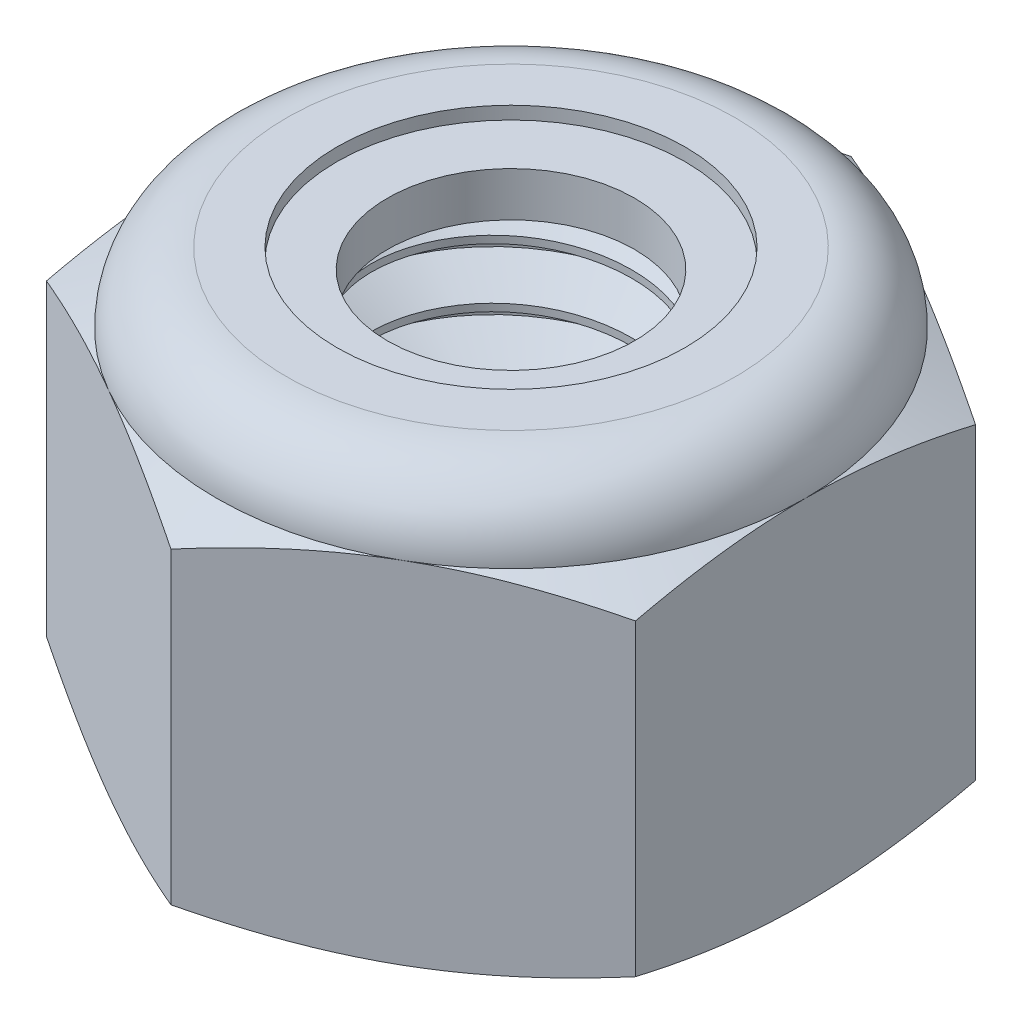
SolidWorks part; units mm, degrees
ref_plane "Front" through (0, 0, 0) normal (0, 0, 1) x (1, 0, 0)
ref_plane "Top" through (0, 0, 0) normal (0, 1, 0) x (1, 0, 0)
ref_plane "Right" through (0, 0, 0) normal (1, 0, 0) x (0, 0, -1)
sketch "Sketch1" plane through (0, 0, 0) normal (0, 1, 0) x (1, 0, 0)
  line L1 (0, 4.0415) -> (-3.5, 2.0207)
  line L2 (-3.5, 2.0207) -> (-3.5, -2.0207)
  line L3 (-3.5, -2.0207) -> (0, -4.0415)
  line L4 (0, -4.0415) -> (3.5, -2.0207)
  line L5 (3.5, -2.0207) -> (3.5, 2.0207)
  line L6 (3.5, 2.0207) -> (0, 4.0415)
  circle A0 centre (0, 0) radius 3.5 construction
  dimension "Hex Flats" = 7
extrude "Extrude1" add sketch "Sketch1" along normal blind 5
sketch "Sketch2" plane through (0, 0, 0) normal (1, 0, 0) x (0, 0, -1)
  line L0 (-2, 0) -> (-2, 5) construction
  line L1 (0, 0) -> (2, 0)
  line L2 (0, 0) -> (0, 5)
  line L3 (0, 5) -> (2, 5)
  line L4 (2, 0) -> (2, 5)
  line L5 (-2.0207, 5) -> (2.0207, 5) construction
  line L7 (0, -2) -> (0, 0) construction
  dimension "Thread Dia" = 4
revolve "Revolve1" add sketch "Sketch2" angle 360 about L7
sketch "Sketch8" plane through (0, 0, 0) normal (0, -1, 0) x (1, 0, 0)
  circle A1 centre (0, 0) radius 2
  circle A2 centre (0, 0) radius 2
  dimension "D1" = 0
curve "Helix/Spiral1" pitch 0.7 height 5.7 turns 8.1429 parameters "Pitch"=0.7
sketch "Sketch10" plane through (0, 0, 0) normal (0, -1, 0) x (1, 0, 0)
  circle A1 centre (0, 0) radius 2
  circle A2 centre (0, 0) radius 2
  dimension "D1" = 0
extrude "Boss-Extrude1" add sketch "Sketch10" against normal through all draft 45
sketch "Sketch11" plane through (0, 5, 0) normal (0, 1, 0) x (1, 0, 0)
  circle A1 centre (0, 0) radius 2
  circle A2 centre (0, 0) radius 2
  dimension "D1" = 0
extrude "Boss-Extrude2" add sketch "Sketch11" against normal through all draft 45
sketch "Sketch9" plane through (0, 0, 0) normal (1, 0, 0) x (0, 0, -1)
  line L0 (2, -0.6125) -> (2, 0)
  line L1 (2, -0.6125) -> (1.5453, -0.35)
  line L2 (1.5453, -0.35) -> (1.5453, -0.2625)
  line L3 (1.5453, -0.2625) -> (2, 0)
  line L4 (-2, 0) -> (2, 0) construction
  line L5 (2, -0.3063) -> (1.5453, -0.3063) construction
  line L6 (1.7727, -0.4813) -> (1.7727, -0.1313) construction
  dimension "D1" = 0.0875
  dimension "D2" = 0.35
  dimension "D3" = 60
sweep "Cut-Sweep1" cut profiles "Sketch9" path "Helix/Spiral1"
combine bodies "Combine1" operation type subtract main body 108 bodies to subtract 132
sketch "Sketch5" plane through (0, 0, 0) normal (1, 0, 0) x (0, 0, -1)
  line L0 (0, 0) -> (3.5, 0)
  line L1 (3.5, 0) -> (4.0415, 0.2525)
  line L2 (4.0415, 0.2525) -> (4.0415, 3.9142)
  line L3 (4.0415, 3.9142) -> (3.5, 4.1667)
  line L4 (2.6667, 5) -> (2.6667, 6.27)
  line L5 (2.6667, 6.27) -> (5.3115, 6.27)
  line L6 (5.3115, 6.27) -> (5.3115, -1.27)
  line L7 (5.3115, -1.27) -> (0, -1.27)
  line L8 (0, -1.27) -> (0, 0)
  line L9 (3.5, 4.1667) -> (3.5, 0) construction
  line L10 (0, 0) -> (2, 0) construction
  line L13 (4.0415, 2.0833) -> (5.3115, 2.0833) construction
  line L14 (4.0415, 5) -> (4.0415, 0) construction
  line L15 (0, 0) -> (0, 6.27) construction
  line L20 (0, 6.27) -> (2.6667, 6.27) construction
  line L22 (0, 5) -> (2, 5) construction
  arc A0 (3.5, 4.1667) -> (2.6667, 5) centre (2.6667, 4.1667) ccw
  dimension "D1" = 25
  dimension "D2" = 1.27
  dimension "D3" = 5
  dimension "D4" = 0.8333
revolve "Cut-Revolve3" cut sketch "Sketch5" angle 360 about L15
sketch "Sketch6" plane through (0, 0, 0) normal (1, 0, 0) x (0, 0, -1)
  line L0 (0, 4.1667) -> (3.3476, 4.1667)
  line L1 (2.6667, 4.8476) -> (2.0681, 4.8476)
  line L2 (0, 6.27) -> (0, 4.1667)
  line L3 (2.0681, 6.27) -> (0, 6.27)
  line L4 (0, 6.27) -> (2.6667, 6.27) construction
  line L5 (0, 0) -> (0, 6.27) construction
  line L6 (0, 6.27) -> (0, 0) construction
  line L7 (2.0681, 4.8476) -> (2.0681, 6.27)
  line L8 (2.6667, 5) -> (2.6667, 4.8476) construction
  line L9 (2.0681, 4.8476) -> (1.4696, 4.8476) construction
  line L10 (1.4696, 4.8476) -> (1.4696, 0) construction
  line L13 (1.4696, 4.6062) -> (2, 4.3) construction
  line L15 (2, 0) -> (2, 5) construction
  line L16 (1.4696, 4.6937) -> (2, 5) construction
  line L19 (1.7348, 4.4531) -> (1.7348, 4.8469) construction
  line L20 (1.4696, 4.6062) -> (1.4696, 4.6937) construction
  line L21 (2, 4.3) -> (2, 5) construction
  line L22 (2, 4.65) -> (1.4696, 4.65) construction
  arc A0 (3.3476, 4.1667) -> (2.6667, 4.8476) centre (2.6667, 4.1667) ccw
  arc A1 (3.5, 4.1667) -> (2.6667, 5) centre (2.6667, 4.1667) ccw construction
  dimension "D1" = 0.1524
  dimension "D2" = 0.7
  dimension "D3" = 0.0875
  dimension "D4" = 60
revolve "Cut-Revolve4" cut sketch "Sketch6" angle 360 about L6
sketch "Sketch7" plane through (0, 0, 0) normal (1, 0, 0) x (0, 0, -1)
  line L0 (1.4696, 4.2429) -> (3.2666, 4.2429)
  line L1 (2.6667, 4.7714) -> (1.4696, 4.7714)
  line L2 (1.4696, 4.7714) -> (1.4696, 4.2429)
  line L3 (1.4696, 4.2429) -> (0, 4.2429) construction
  line L4 (0, 4.2429) -> (0, 4.7714) construction
  line L5 (0, 4.7714) -> (1.4696, 4.7714) construction
  line L6 (1.4696, 4.2429) -> (1.4696, 4.1667) construction
  line L7 (0, 4.1667) -> (3.3476, 4.1667) construction
  line L8 (2.6667, 4.7714) -> (2.6667, 4.8476) construction
  line L9 (1.4696, 4.8476) -> (1.4696, 0) construction
  arc A0 (3.2666, 4.2429) -> (2.6667, 4.7714) centre (2.6667, 4.1667) ccw
  arc A2 (3.3476, 4.1667) -> (2.6667, 4.8476) centre (2.6667, 4.1667) ccw construction
  dimension "D1" = 0.0762
revolve "Revolve2" add sketch "Sketch7" angle 360 about L4
equation "\"D4@Sketch5\"=\"Height@Extrude1\"/6"
equation "\"D3@Helix/Spiral1\"=\"Pitch@Helix/Spiral1\"+\"Height@Extrude1\""
equation "\"D1@Sketch9\"=\"Pitch@Helix/Spiral1\"*.125"
equation "\"D2@Sketch9\"=\"Pitch@Helix/Spiral1\"*.50"
equation "\"D2@Sketch6\"=\"Pitch@Helix/Spiral1\""
equation "\"D3@Sketch6\"=\"Pitch@Helix/Spiral1\"/8"
